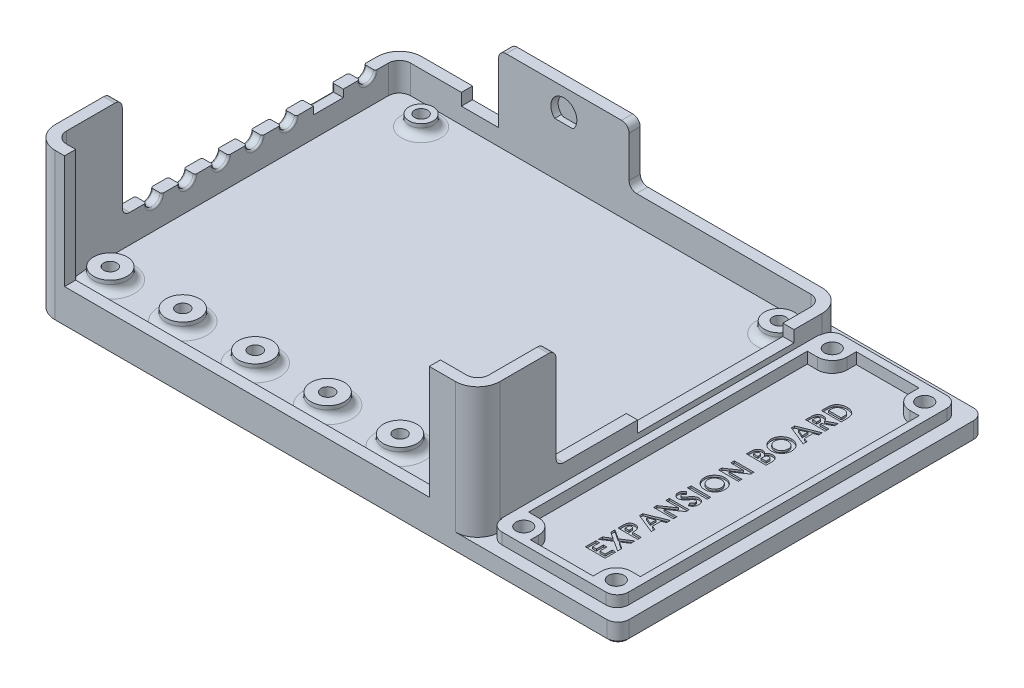
SolidWorks part; units mm, degrees
ref_plane "Front Plane" through (0, 0, 0) normal (0, 0, 1) x (1, 0, 0)
ref_plane "Top Plane" through (0, 0, 0) normal (0, 1, 0) x (1, 0, 0)
ref_plane "Right Plane" through (0, 0, 0) normal (1, 0, 0) x (0, 0, -1)
sketch "Sketch1" plane through (0, 0, 0) normal (0, 1, 0) x (1, 0, 0)
  line L1 (-53.7, 46.2) -> (53.7, 46.2)
  line L2 (-56.7, 43.2) -> (-56.7, -43.2)
  line L3 (-53.7, -46.2) -> (53.7, -46.2)
  line L4 (56.7, 43.2) -> (56.7, -43.2)
  line L5 (-56.7, 46.2) -> (56.7, -46.2) construction
  line L6 (-56.7, -46.2) -> (56.7, 46.2) construction
  arc A0 (-56.7, -43.2) -> (-53.7, -46.2) centre (-53.7, -43.2) ccw
  arc A1 (53.7, -46.2) -> (56.7, -43.2) centre (53.7, -43.2) ccw
  arc A2 (53.7, 46.2) -> (56.7, 43.2) centre (53.7, 43.2) cw
  arc A3 (-53.7, 46.2) -> (-56.7, 43.2) centre (-53.7, 43.2) ccw
  point P0 (0, 0)
  dimension "D3" = 3
  dimension "D1" = 113.4
  dimension "D2" = 92.4
extrude "Boss-Extrude1" add sketch "Sketch1" along normal blind 5
sketch "Sketch2" plane through (0, 0, 0) normal (0, -1, 0) x (1, 0, 0)
  line L12 (-56.7, 43.2) -> (-56.7, -43.2)
  line L13 (-53.7, -46.2) -> (53.7, -46.2)
  line L14 (56.7, -43.2) -> (56.7, 43.2)
  line L15 (53.7, 46.2) -> (-53.7, 46.2)
  line L16 (-56.7, 43.2) -> (-56.7, -43.2)
  line L17 (-53.7, -46.2) -> (53.7, -46.2)
  line L18 (56.7, -43.2) -> (56.7, 43.2)
  line L19 (53.7, 46.2) -> (-53.7, 46.2)
  line L24 (-59.7, 43.2) -> (-59.7, -43.2)
  line L25 (-53.7, -49.2) -> (53.7, -49.2)
  line L26 (59.7, -43.2) -> (59.7, 43.2)
  line L27 (53.7, 49.2) -> (-53.7, 49.2)
  line L28 (-59.7, 43.2) -> (-59.7, -43.2)
  line L29 (-53.7, -49.2) -> (53.7, -49.2)
  line L30 (59.7, -43.2) -> (59.7, 43.2)
  line L31 (53.7, 49.2) -> (-53.7, 49.2)
  arc A12 (-53.7, 46.2) -> (-56.7, 43.2) centre (-53.7, 43.2) ccw
  arc A13 (-56.7, -43.2) -> (-53.7, -46.2) centre (-53.7, -43.2) ccw
  arc A14 (53.7, -46.2) -> (56.7, -43.2) centre (53.7, -43.2) ccw
  arc A15 (56.7, 43.2) -> (53.7, 46.2) centre (53.7, 43.2) ccw
  arc A16 (-53.7, 46.2) -> (-56.7, 43.2) centre (-53.7, 43.2) ccw
  arc A17 (-56.7, -43.2) -> (-53.7, -46.2) centre (-53.7, -43.2) ccw
  arc A18 (53.7, -46.2) -> (56.7, -43.2) centre (53.7, -43.2) ccw
  arc A19 (56.7, 43.2) -> (53.7, 46.2) centre (53.7, 43.2) ccw
  arc A24 (-53.7, 49.2) -> (-59.7, 43.2) centre (-53.7, 43.2) ccw
  arc A25 (-59.7, -43.2) -> (-53.7, -49.2) centre (-53.7, -43.2) ccw
  arc A26 (53.7, -49.2) -> (59.7, -43.2) centre (53.7, -43.2) ccw
  arc A27 (59.7, 43.2) -> (53.7, 49.2) centre (53.7, 43.2) ccw
  arc A28 (-53.7, 49.2) -> (-59.7, 43.2) centre (-53.7, 43.2) ccw
  arc A29 (-59.7, -43.2) -> (-53.7, -49.2) centre (-53.7, -43.2) ccw
  arc A30 (53.7, -49.2) -> (59.7, -43.2) centre (53.7, -43.2) ccw
  arc A31 (59.7, 43.2) -> (53.7, 49.2) centre (53.7, 43.2) ccw
  dimension "D1" = 0
  dimension "D2" = 3
extrude "Boss-Extrude2" add sketch "Sketch2" against normal blind 40
sketch "Sketch3" plane through (0, 0, 0) normal (0, -1, 0) x (1, 0, 0)
  line L0 (53.7, 49.2) -> (-53.7, 49.2) construction
  line L1 (39.3485, 49.2) -> (98.7, 49.2)
  line L2 (39.3485, 49.2) -> (39.3485, -49.2)
  line L3 (39.3485, -49.2) -> (98.7, -49.2)
  line L4 (98.7, 49.2) -> (98.7, -49.2)
  line L5 (59.7, -43.2) -> (59.7, 43.2) construction
  line L6 (-53.7, -49.2) -> (53.7, -49.2) construction
  dimension "D1" = 39
extrude "Boss-Extrude3" add sketch "Sketch3" against normal blind 5
sketch "Sketch4" plane through (0, 40, 0) normal (0, 1, 0) x (1, 0, 0)
  line L0 (-56.7, 43.2) -> (-56.7, -43.2) construction
  line L1 (-51.2, -37.1427) -> (46.7, -37.1427)
  line L2 (-51.2, -37.1427) -> (-51.2, -59.8991)
  line L3 (-51.2, -59.8991) -> (46.7, -59.8991)
  line L4 (46.7, -37.1427) -> (46.7, -59.8991)
  line L5 (56.7, 43.2) -> (56.7, -43.2) construction
  dimension "D1" = 5.5
  dimension "D2" = 10
extrude "Cut-Extrude1" cut sketch "Sketch4" against normal offset from surface (30.4 mm away) 4.6 up to face at (0, 5, 0)
sketch "Sketch7" plane through (0, 5, 0) normal (0, 1, 0) x (1, 0, 0)
  line L0 (-51.3, -36.8) -> (45.92, -36.8) construction
  line L1 (51.042, 40.404) -> (-45.097, 40.404) construction
  line L3 (-56.7, 0) -> (56.7, 0) construction
  line L4 (-56.7, -43.2) -> (-56.7, 43.2) construction
  line L5 (56.7, -43.2) -> (56.7, 43.2) construction
  line L6 (-56.7, 43.2) -> (-56.7, -43.2) construction
  line L7 (0, 46.2) -> (0, -46.2) construction
  line L8 (-53.7, 46.2) -> (53.7, 46.2) construction
  line L9 (-53.7, -46.2) -> (53.7, -46.2) construction
  line L10 (46.7, -46.2) -> (-51.2, -46.2) construction
  circle A0 centre (-51.3, -36.8) radius 1.75
  circle A1 centre (-31.86, -36.8) radius 1.75
  circle A2 centre (-12.41, -36.8) radius 1.75
  circle A3 centre (7.03, -36.8) radius 1.75
  circle A4 centre (26.46, -36.8) radius 1.75
  circle A5 centre (45.92, -36.8) radius 1.75
  circle A6 centre (-45.097, 40.404) radius 1.75
  circle A7 centre (51.042, 40.404) radius 1.75
  circle A8 centre (-45.097, 40.404) radius 3.25
  circle A9 centre (51.042, 40.404) radius 4
  circle A10 centre (45.92, -36.8) radius 4.5
  circle A11 centre (26.46, -36.8) radius 4.5
  circle A12 centre (7.03, -36.8) radius 4.5
  circle A13 centre (-12.41, -36.8) radius 4.5
  circle A14 centre (-31.86, -36.8) radius 4.5
  circle A15 centre (-51.3, -36.8) radius 4.5
  dimension "D1" = 3.5
  dimension "D2" = 3.5
  dimension "D3" = 3.5
  dimension "D4" = 3.5
  dimension "D5" = 3.5
  dimension "D6" = 3.5
  dimension "D7" = 3.5
  dimension "D8" = 3.5
  dimension "D19" = 9
  dimension "D20" = 9
  dimension "D21" = 9
  dimension "D22" = 9
  dimension "D23" = 9
  dimension "D24" = 9
  dimension "D25" = 8
  dimension "D26" = 6.5
  dimension "D9" = 77.204
  dimension "D10" = 6.203
  dimension "D11" = 5.122
  dimension "D12" = 19.44
  dimension "D13" = 19.45
  dimension "D14" = 19.44
  dimension "D15" = 19.43
  dimension "D16" = 19.46
  dimension "D17" = 5.4
  dimension "D18" = 9.4
extrude "Boss-Extrude5" add sketch "Sketch7" along normal offset from surface (3 mm away) 1.6 up to face at (-2.25, 9.6, 47.7)
fillet "Fillet2" radius 2 8 edges at (45.92, 5, 41.3) (26.46, 5, 41.3) (7.03, 5, 41.3) (-12.41, 5, 41.3) (-31.86, 5, 41.3) (-51.3, 5, 41.3) (51.042, 5, -36.404) (-45.097, 5, -37.154)
sketch "Sketch11" plane through (-59.7, 0, 0) normal (-1, 0, 0) x (0, 0, 1)
  line L0 (-37.613, 12.6) -> (19.667, 12.6) construction
  line L1 (43.2, 0) -> (-43.2, 0) construction
  line L3 (-37.613, 12.6) -> (-43.2, 12.6) construction
  line L4 (-43.2, 40) -> (-43.2, 0) construction
  circle A0 centre (19.667, 12.6) radius 2.1
  circle A1 centre (10.777, 12.6) radius 2.1
  circle A2 centre (1.757, 12.6) radius 2.1
  circle A3 centre (-7.26, 12.6) radius 2.1
  circle A4 centre (-16.404, 12.6) radius 2.1
  circle A5 centre (-37.613, 12.6) radius 2.1
  dimension "D7" = 4.2
  dimension "D8" = 4.2
  dimension "D9" = 4.2
  dimension "D10" = 4.2
  dimension "D11" = 4.2
  dimension "D12" = 4.2
  dimension "D1" = 12.6
  dimension "D2" = 21.209
  dimension "D3" = 9.144
  dimension "D4" = 9.017
  dimension "D5" = 9.02
  dimension "D6" = 8.89
  dimension "D13" = 5.587
extrude "Cut-Extrude4" cut sketch "Sketch11" against normal blind 9.6
sketch "Sketch12" plane through (-59.7, 0, 0) normal (-1, 0, 0) x (0, 0, 1)
  line L0 (43.2, 40) -> (-43.2, 40) construction
  line L1 (28.2, 40) -> (-56.9577, 40)
  line L2 (28.2, 40) -> (28.2, 12.6)
  line L3 (28.2, 12.6) -> (-56.9577, 12.6)
  line L4 (-56.9577, 40) -> (-56.9577, 12.6)
  line L5 (43.2, 0) -> (-43.2, 0) construction
  dimension "D1" = 21
  dimension "D2" = 12.6
extrude "Cut-Extrude5" cut sketch "Sketch12" against normal through all
sketch "Sketch13" plane through (0, 12.6, 0) normal (0, 1, 0) x (1, 0, 0)
  line L0 (-45.097, 40.404) -> (-35.077, 40.404) construction
  line L2 (-40.077, 53.0138) -> (-30.077, 53.0138)
  line L3 (-40.077, 53.0138) -> (-40.077, 27.7942)
  line L4 (-40.077, 27.7942) -> (-30.077, 27.7942)
  line L5 (-30.077, 53.0138) -> (-30.077, 27.7942)
  line L6 (-40.077, 53.0138) -> (-30.077, 27.7942) construction
  line L7 (-40.077, 27.7942) -> (-30.077, 53.0138) construction
  dimension "D1" = 10.02
  dimension "D2" = 10
extrude "Cut-Extrude6" cut sketch "Sketch13" against normal offset from surface (3.2 mm away) 1.4 up to face at (-45.097, 8, -38.654)
sketch "Sketch14" plane through (0, 12.6, 0) normal (0, 1, 0) x (1, 0, 0)
  line L0 (51.042, 40.404) -> (51.042, 35.704) construction
  line L1 (45.5852, 35.704) -> (71.3808, 35.704)
  line L2 (45.5852, 35.704) -> (45.5852, -6.296)
  line L3 (45.5852, -6.296) -> (71.3808, -6.296)
  line L4 (71.3808, 35.704) -> (71.3808, -6.296)
  dimension "D1" = 42
  dimension "D2" = 4.7
extrude "Cut-Extrude7" cut sketch "Sketch14" against normal offset from surface (3.1 mm away) 1.5 up to face at (51.042, 8, -38.654)
sketch "Sketch15" plane through (0, 12.6, 0) normal (0, 1, 0) x (1, 0, 0)
  line L0 (53.7, 46.2) -> (-30.077, 46.2) construction
  line L1 (-30.077, 49.2) -> (4.923, 49.2)
  line L2 (-30.077, 49.2) -> (-30.077, 46.2)
  line L3 (-30.077, 46.2) -> (4.923, 46.2)
  line L4 (4.923, 49.2) -> (4.923, 46.2)
  dimension "D1" = 35
extrude "Boss-Extrude6" add sketch "Sketch15" along normal blind 15
fillet "Fillet3" radius 2 7 edges at (-58.2, 40, 28.2) (58.2, 40, 28.2) (58.2, 12.6, 28.2) (4.923, 12.6, -47.7) (4.923, 27.6, -47.7) (-30.077, 27.6, -47.7) (-58.2, 12.6, 28.2)
sketch "Sketch16" plane through (0, 0, -49.2) normal (0, 0, -1) x (-1, 0, 0)
  line L0 (10.1275, 19.1) -> (15.0265, 19.1)
  line L2 (-46.7, 9.6) -> (51.2, 9.6) construction
  line L3 (30.077, 25.6) -> (30.077, 9.4) construction
  arc A0 (15.0265, 19.1) -> (10.1275, 19.1) centre (12.577, 21.6) ccw
  dimension "D1" = 7
  dimension "D2" = 2.5
  dimension "D3" = 12
  dimension "D4" = 17.5
extrude "Cut-Extrude8" cut sketch "Sketch16" against normal up to surface (3 mm away) up to face at (-3.1349, 14.0416, -46.2)
sketch "Sketch17" plane through (0, 0, -49.2) normal (0, 0, -1) x (-1, 0, 0)
  circle A0 centre (12.577, 21.6) radius 3.0287
extrude "Boss-Extrude7" add sketch "Sketch17" against normal blind 1.5
sketch "Sketch18" plane through (0, 8, 0) normal (0, 1, 0) x (1, 0, 0)
  circle A0 centre (-51.3, -36.8) radius 1.75
  circle A1 centre (-31.86, -36.8) radius 1.75
  circle A2 centre (-12.41, -36.8) radius 1.75
  circle A3 centre (7.03, -36.8) radius 1.75
  circle A4 centre (26.46, -36.8) radius 1.75
  circle A5 centre (45.92, -36.8) radius 1.75
  circle A6 centre (51.042, 40.404) radius 1.75
  circle A7 centre (-45.097, 40.404) radius 1.75
extrude "Cut-Extrude9" cut sketch "Sketch18" against normal through all
sketch "Sketch19" plane through (0, 0, 0) normal (0, -1, 0) x (1, 0, 0)
  circle A0 centre (-51.3, 36.8) radius 2.9
  circle A1 centre (-31.86, 36.8) radius 2.9
  circle A2 centre (-12.41, 36.8) radius 2.9
  circle A3 centre (7.03, 36.8) radius 2.9
  circle A4 centre (26.46, 36.8) radius 2.9
  circle A5 centre (45.92, 36.8) radius 2.9
  circle A6 centre (51.042, -40.404) radius 2.9
  circle A7 centre (-45.097, -40.404) radius 2.9
  dimension "D1" = 5.8
  dimension "D2" = 5.8
  dimension "D3" = 5.8
  dimension "D4" = 5.8
  dimension "D5" = 5.8
  dimension "D6" = 5.8
  dimension "D7" = 5.8
  dimension "D8" = 5.8
extrude "Cut-Extrude10" cut sketch "Sketch19" against normal offset from surface (3.5 mm away) 1.5 up to face at (45.92, 5, 43.3)
sketch "Sketch20" plane through (0, 5, 0) normal (0, 1, 0) x (1, 0, 0)
  line L0 (64.6, 41.068) -> (64.6, -41.736) construction
  line L1 (64.6, -41.736) -> (89.428, -41.736) construction
  line L2 (89.428, -41.736) -> (89.428, 41.068) construction
  line L3 (89.428, 41.068) -> (64.6, 41.068) construction
  line L4 (59.7, -43.2) -> (59.7, 43.2) construction
  line L5 (62.9, 45.513) -> (90.9, 45.513)
  line L6 (59.9, 42.513) -> (59.9, -42.937)
  line L7 (62.9, -45.937) -> (90.9, -45.937)
  line L8 (93.9, 42.513) -> (93.9, -42.937)
  line L9 (51.042, 40.404) -> (51.042, 34.21) construction
  line L10 (51.042, 34.21) -> (76.3886, 34.21) construction
  line L11 (76.3886, 34.21) -> (76.3886, 41.068) construction
  line L12 (61.9, 37.068) -> (61.9, -37.736)
  line L13 (68.6, -43.937) -> (85.428, -43.937)
  line L14 (91.9, 37.068) -> (91.9, -37.736)
  line L16 (64.6, 37.068) -> (61.9, 37.068)
  line L17 (68.6, 41.068) -> (68.6, 43.513)
  line L18 (85.428, 41.068) -> (85.428, 43.513)
  line L19 (89.428, 37.068) -> (91.9, 37.068)
  line L20 (64.6, -37.736) -> (61.9, -37.736)
  line L21 (68.6, -41.736) -> (68.6, -43.937)
  line L22 (85.428, -41.736) -> (85.428, -43.937)
  line L23 (89.428, -37.736) -> (91.9, -37.736)
  line L24 (62.9, -43.937) -> (90.9, -43.937) construction
  line L25 (61.9, 42.513) -> (61.9, -42.937) construction
  line L26 (91.9, 42.513) -> (91.9, -42.937) construction
  line L27 (62.9, 43.513) -> (90.9, 43.513) construction
  line L28 (68.6, 43.513) -> (85.428, 43.513)
  circle A0 centre (64.6, 41.068) radius 2.1
  circle A1 centre (89.428, 41.068) radius 2.1
  circle A2 centre (89.428, -41.736) radius 2.1
  circle A3 centre (64.6, -41.736) radius 2.1
  arc A4 (59.9, -42.937) -> (62.9, -45.937) centre (62.9, -42.937) ccw
  arc A5 (90.9, -45.937) -> (93.9, -42.937) centre (90.9, -42.937) ccw
  arc A6 (90.9, 45.513) -> (93.9, 42.513) centre (90.9, 42.513) cw
  arc A7 (62.9, 45.513) -> (59.9, 42.513) centre (62.9, 42.513) ccw
  arc A12 (64.6, 37.068) -> (68.6, 41.068) centre (64.6, 41.068) ccw
  arc A13 (85.428, 41.068) -> (89.428, 37.068) centre (89.428, 41.068) ccw
  arc A14 (68.6, -41.736) -> (64.6, -37.736) centre (64.6, -41.736) ccw
  arc A15 (89.428, -37.736) -> (85.428, -41.736) centre (89.428, -41.736) ccw
  arc A16 (61.9, -42.937) -> (62.9, -43.937) centre (62.9, -42.937) ccw construction
  arc A17 (90.9, -43.937) -> (91.9, -42.937) centre (90.9, -42.937) ccw construction
  arc A18 (90.9, 43.513) -> (91.9, 42.513) centre (90.9, 42.513) cw construction
  arc A19 (62.9, 43.513) -> (61.9, 42.513) centre (62.9, 42.513) ccw construction
  point P23 (93.9, -45.937)
  point P26 (93.9, 45.513)
  point P29 (59.9, 45.513)
  dimension "D10" = 3
  dimension "D12" = 8
  dimension "D13" = 8
  dimension "D14" = 8
  dimension "D15" = 8
  dimension "D16" = 4.2
  dimension "D17" = 4.2
  dimension "D18" = 4.2
  dimension "D19" = 4.2
  dimension "D1" = 82.804
  dimension "D2" = 24.828
  dimension "D3" = 4.445
  dimension "D4" = 4.7
  dimension "D5" = 34
  dimension "D6" = 0.2
  dimension "D7" = 6.194
  dimension "D8" = 6.858
  dimension "D9" = 91.45
  dimension "D11" = 2
extrude "Boss-Extrude8" add sketch "Sketch20" along normal up to surface (3 mm away) up to face at (45.92, 8, 38.55)
sketch "Sketch21" plane through (0, 5, 0) normal (0, 1, 0) x (1, 0, 0)
  line L0 (79.8859, -35.8007) -> (79.8859, 35.1839) construction
  text T0 "<b>EXPANSION BOARD</b>" font "Century Gothic" height in points 20
extrude "Cut-Extrude11" cut sketch "Sketch21" against normal blind 0.5
sketch "Sketch22" plane through (0, 5, 0) normal (0, 1, 0) x (1, 0, 0)
  line L0 (93.9, -42.937) -> (93.9, 42.513) construction
  line L1 (97.35, 52.1113) -> (108.1813, 52.1113)
  line L2 (97.35, 52.1113) -> (97.35, -51.7076)
  line L3 (97.35, -51.7076) -> (108.1813, -51.7076)
  line L4 (108.1813, 52.1113) -> (108.1813, -51.7076)
  dimension "D1" = 3.45
extrude "Cut-Extrude12" cut sketch "Sketch22" against normal through all
fillet "Fillet4" radius 3 2 edges at (97.35, 2.5, 49.2) (97.35, 2.5, -49.2)
chamfer "Chamfer1" distance 0.6 angle 45 16 edges at (96.4713, 0, -48.3213) (20.325, 0, -49.2) (-57.9426, 0, -47.4426) (-59.7, 0, 0) (-57.9426, 0, 47.4426) (20.325, 0, 49.2) (96.4713, 0, 48.3213) (97.35, 0, 0) (-31.86, 0, 33.9) (-12.41, 0, 33.9) (7.03, 0, 33.9) (26.46, 0, 33.9) (45.92, 0, 33.9) (51.042, 0, -43.304) (-45.097, 0, -43.304) (-51.3, 0, 33.9)
sketch "Sketch23" plane through (0, 5, 0) normal (0, 1, 0) x (1, 0, 0)
  circle A0 centre (64.6, 41.068) radius 2.1
  circle A1 centre (89.428, 41.068) radius 2.1
  circle A2 centre (64.6, -41.736) radius 2.1
  circle A3 centre (89.428, -41.736) radius 2.1
extrude "Cut-Extrude13" cut sketch "Sketch23" against normal offset from surface (3 mm away) 2 up to face at (19.4197, 0, 0)
sketch "Sketch26" plane through (0, 8, 0) normal (0, 1, 0) x (1, 0, 0)
  line L1 (59.9, 42.513) -> (58.6453, 42.513)
  line L2 (59.9, 42.513) -> (59.9, -42.937)
  line L3 (59.9, -42.937) -> (58.6453, -42.937)
  line L4 (58.6453, 42.513) -> (58.6453, -42.937)
extrude "Boss-Extrude10" add sketch "Sketch26" against normal up to surface (8 mm away) up to face at (19.4197, 0, 0)
fillet "Fillet5" radius 0.5 12 edges at (-59.7, 10.5, -37.613) (-59.7, 10.5, -16.404) (-59.7, 10.5, -7.26) (-59.7, 10.5, 1.757) (-59.7, 10.5, 10.777) (-59.7, 10.5, 19.667) (-56.7, 10.5, 19.667) (-56.7, 10.5, 10.777) (-56.7, 10.5, 1.757) (-56.7, 10.5, -7.26) (-56.7, 10.5, -16.404) (-56.7, 10.5, -37.613)
sketch "Sketch29" plane through (0, 12.6, 0) normal (0, 1, 0) x (1, 0, 0)
  line L0 (-56.7, 31.1209) -> (-59.7, 31.1209)
  line L1 (-56.7, 35.013) -> (-56.7, 19.004) construction
  line L2 (-59.7, 35.013) -> (-59.7, 19.004) construction
  line L3 (-59.7, 31.1209) -> (-59.7, 23.1157)
  line L4 (-59.7, 23.1157) -> (-56.7, 23.1157)
  line L5 (-56.7, 23.1157) -> (-56.7, 31.1209)
extrude "Cut-Extrude14" cut sketch "Sketch29" against normal blind 2
fillet "Fillet6" radius 0.5 3 edges at (-59.7, 10.6, -27.1183) (-59.7, 11.6, -23.1157) (-59.7, 11.6, -31.1209)
